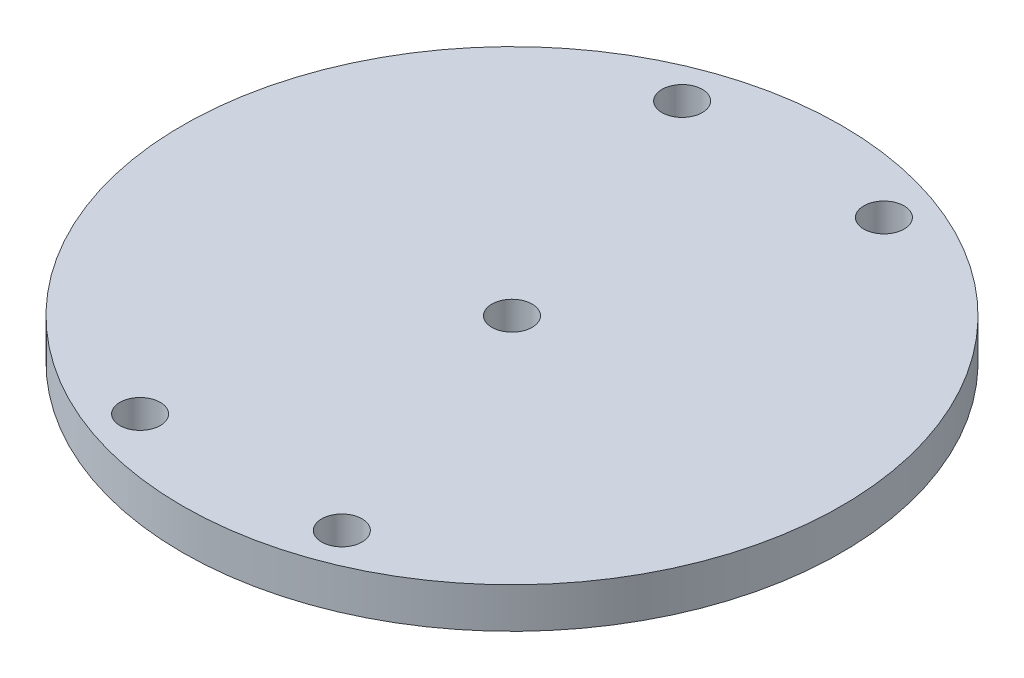
SolidWorks part; units mm, degrees
ref_plane "Front Plane" through (0, 0, 0) normal (0, 0, 1) x (1, 0, 0)
ref_plane "Top Plane" through (0, 0, 0) normal (0, 1, 0) x (1, 0, 0)
ref_plane "Right Plane" through (0, 0, 0) normal (1, 0, 0) x (0, 0, -1)
sketch "Sketch1" plane through (0, 0, 0) normal (0, 1, 0) x (1, 0, 0)
  circle A0 centre (0, 0) radius 49
  dimension "D1" = 98
extrude "Boss-Extrude1" add sketch "Sketch1" along normal blind 6
sketch "Sketch2" plane through (0, 6, 0) normal (0, 1, 0) x (1, 0, 0)
  circle A0 centre (0, 0) radius 3
  circle A1 centre (-15, 40.2989) radius 3
  circle A2 centre (15, 40.2989) radius 3
  circle A3 centre (-15, -40.2989) radius 3
  circle A4 centre (15, -40.2989) radius 3
  arc A5 (-17.7733, 39.1549) -> (-17.7733, -39.1549) centre (0, 0) ccw
  arc A6 (12.1537, 41.2467) -> (-12.1537, 41.2467) centre (0, 0) ccw
  arc A7 (17.7733, -39.1549) -> (17.7733, 39.1549) centre (0, 0) ccw
  arc A8 (-12.1537, -41.2467) -> (12.1537, -41.2467) centre (0, 0) ccw
  dimension "D1" = 6
  dimension "D2" = 6
  dimension "D3" = 6
  dimension "D4" = 6
  dimension "D5" = 6
  dimension "D6" = 86
  dimension "D7" = 30
  dimension "D8" = 30
  dimension "D9" = 15
  dimension "D10" = 15
extrude "Cut-Extrude1" cut sketch "Sketch2" against normal blind 6 contours A1 | A2 | A0 | A4 | A3 region at (0, 6, 0) region at (-15, 6, -40.2989) region at (15, 6, -40.2989) region at (-15, 6, 40.2989) region at (15, 6, 40.2989)
cosmetic thread "Cosmetic Thread1" parameters "D2"=7.2
cosmetic thread "Cosmetic Thread2" parameters "D2"=7.2
cosmetic thread "Cosmetic Thread3" parameters "D2"=7.2
cosmetic thread "Cosmetic Thread4" parameters "D2"=7.2
cosmetic thread "Cosmetic Thread5" parameters "D2"=7.2
